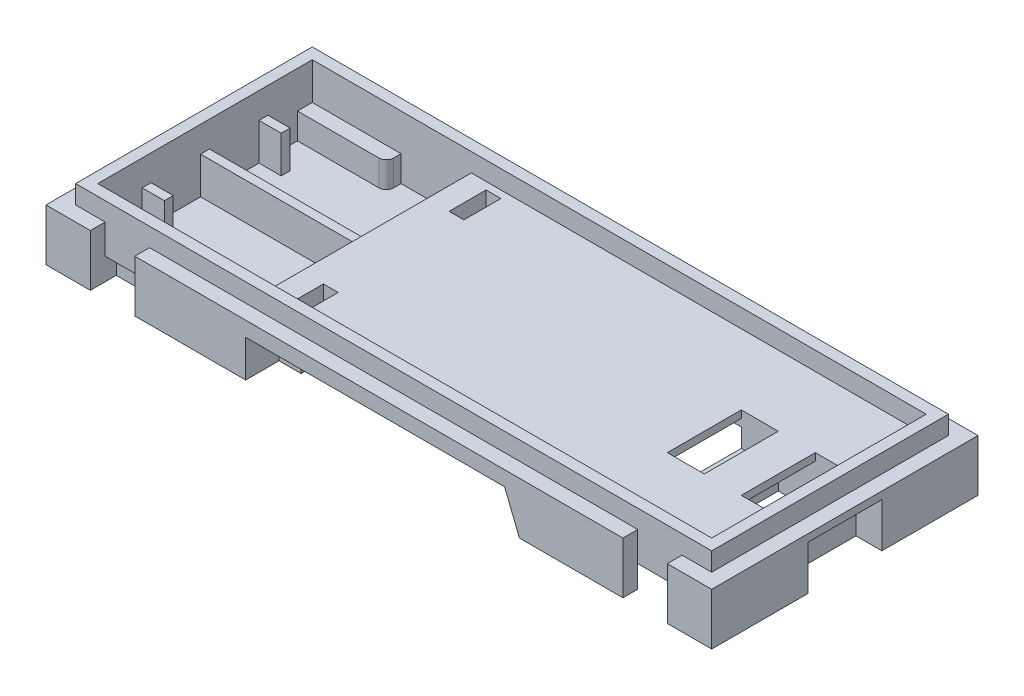
SolidWorks part; units mm, degrees
ref_plane "Спереди" through (0, 0, 0) normal (0, 0, 1) x (1, 0, 0)
ref_plane "Сверху" through (0, 0, 0) normal (0, 1, 0) x (1, 0, 0)
ref_plane "Справа" through (0, 0, 0) normal (1, 0, 0) x (0, 0, -1)
sketch "Эскиз1" plane through (0, 0, 0) normal (0, 1, 0) x (1, 0, 0)
  line L1 (45, -18) -> (-45, -18)
  line L2 (45, -18) -> (45, 18)
  line L3 (45, 18) -> (-45, 18)
  line L4 (-45, -18) -> (-45, 18)
  line L5 (45, -18) -> (-45, 18) construction
  line L6 (45, 18) -> (-45, -18) construction
  point P0 (0, 0)
  dimension "D1" = 90
  dimension "D2" = 36
extrude "Бобышка-Вытянуть1" add sketch "Эскиз1" along normal blind 7
sketch "Эскиз2" plane through (0, 7, 0) normal (0, 1, 0) x (1, 0, 0)
  line L1 (43, -16) -> (-43, -16)
  line L2 (43, -16) -> (43, 16)
  line L3 (43, 16) -> (-43, 16)
  line L4 (-43, -16) -> (-43, 16)
  line L5 (43, -16) -> (-43, 16) construction
  line L6 (43, 16) -> (-43, -16) construction
  point P0 (0, 0)
  dimension "D1" = 2
  dimension "D2" = 2
extrude "Вытянуть-Тонкостенный1" add sketch "Эскиз2" along normal blind 2.5 thin thin type one direction reverse wall 1.5
sketch "Эскиз3" plane through (0, 0, 18) normal (0, 0, 1) x (1, 0, 0)
  line L0 (-45, 0) -> (-18, 0) construction
  line L1 (-45, 0) -> (45, 0) construction
  line L2 (-18, 0) -> (-18, 5)
  line L3 (-18, 5) -> (17, 5)
  line L4 (17, 5) -> (19, 0)
  line L5 (-18, 0) -> (19, 0)
  dimension "D1" = 27
  dimension "D2" = 35
  dimension "D3" = 37
  dimension "D4" = 5
extrude "Вырез-Вытянуть1" cut sketch "Эскиз3" against normal up to surface (36 mm away) up to face at (0, 3.5, -18)
sketch "Эскиз4" plane through (45, 0, 0) normal (1, 0, 0) x (0, 0, -1)
  line L0 (0, 0) -> (0, 2.5) construction
  line L1 (-5, 2.5) -> (5, 2.5)
  line L2 (-5, 6) -> (5, 6)
  line L3 (-5, 6) -> (-5, 0)
  line L4 (-5, 0) -> (5, 0)
  line L5 (5, 6) -> (5, 0)
  point P7 (0, 0)
  line M2 (-18, 0) -> (18, 0)
  dimension "D1" = 2.5
  dimension "D2" = 6
  dimension "D3" = 10
  dimension "D4" = 2.5
extrude "Вырез-Вытянуть2" cut sketch "Эскиз4" against normal blind 3.5 contours L0 L1 L3 M2 | L0 L4 L5 L1 | L5 L2 L3 L1 region at (45, 1.25, 2.5) region at (45, 1.25, -2.5) region at (45, 4.25, 0)
extrude "Вырез-Вытянуть3" cut sketch "Эскиз4<3>" against normal blind 52 contours L5 L2 L3 L1 region at (45, 4.25, 0)
sketch "Эскиз4<3>" plane through (45, 0, 0) normal (1, 0, 0) x (0, 0, -1) same geometry as "Эскиз4"
sketch "Эскиз5" plane through (0, 0, 0) normal (0, -1, 0) x (1, 0, 0)
  line L0 (0, 0) -> (45, 0) construction
  line L1 (45, 5) -> (45, -5) construction
  line L2 (45, -7) -> (45, 7)
  line L3 (43, -16) -> (13, -16)
  line L4 (43, -16) -> (43, 16)
  line L5 (43, 16) -> (13, 16)
  line L6 (13, -16) -> (13, 16)
  line L7 (43, -16) -> (13, 16) construction
  line L8 (43, 16) -> (13, -16) construction
  line L9 (45, 18) -> (45, 5) construction
  line L10 (45, 7) -> (26, 7)
  line L11 (26, 7) -> (26, -7)
  line L12 (26, -7) -> (45, -7)
  line L13 (26, 0) -> (31, 0) construction
  line L14 (36, -5) -> (31, -5)
  line L15 (36, -5) -> (36, 5)
  line L16 (36, 5) -> (31, 5)
  line L17 (31, -5) -> (31, 5)
  line L18 (36, -5) -> (31, 5) construction
  line L19 (36, 5) -> (31, -5) construction
  point P5 (28, 0)
  point P10 (33.5, 0)
  point P16 (45, 0)
  line M10 (19, 18) -> (19, -18)
  dimension "D1" = 2
  dimension "D2" = 2
  dimension "D3" = 30
  dimension "D4" = 14
  dimension "D5" = 19
  dimension "D6" = 5
  dimension "D7" = 10
  dimension "D8" = 5
extrude "Вырез-Вытянуть4" cut sketch "Эскиз5" against normal up to surface (5 mm away) contours L12 L11 L10 L4 L5 L3 M10 | L6 L3 L5 M10 | L17 L14 L15 L16 region at (42.6, 0, -11.5) region at (16, 0, 0) region at (33.5, 0, 0) up to face at (2.25, 5, 0)
sketch "Эскиз6" plane through (0, 7, 0) normal (0, 1, 0) x (1, 0, 0)
  line L0 (-41.5, -14.5) -> (41.5, -14.5) construction
  line L1 (-41.5, 14.5) -> (-20, 14.5)
  line L2 (-41.5, 14.5) -> (-41.5, -14.5)
  line L3 (-41.5, -14.5) -> (-20, -14.5)
  line L4 (-20, 14.5) -> (-20, -14.5)
  dimension "D1" = 21.5
extrude "Вырез-Вытянуть5" cut sketch "Эскиз6" against normal blind 6
sketch "Эскиз7" plane through (0, 5, 0) normal (0, -1, 0) x (1, 0, 0)
  line L0 (43, 16) -> (17, 16) construction
  line L1 (24, 16) -> (20.5, 16)
  line L2 (24, 16) -> (24, 12)
  line L3 (24, 12) -> (20.5, 12)
  line L4 (20.5, 16) -> (20.5, 12)
  line L5 (43, 16) -> (19, 16) construction
  line L6 (45, 0) -> (0, 0) construction
  line L7 (45, 5) -> (45, -5) construction
  line L8 (24, -16) -> (20.5, -16)
  line L9 (24, -16) -> (24, -12)
  line L10 (24, -12) -> (20.5, -12)
  line L11 (20.5, -16) -> (20.5, -12)
  arc A0 (20.5, 14) -> (24, 14) centre (22.25, 13.7656) ccw
  arc A1 (20.5, -14) -> (24, -14) centre (22.25, -13.7656) cw
  line M7 (17, -16) -> (43, -16)
  line M17 (43, 16) -> (17, 16)
  dimension "D1" = 19
  dimension "D2" = 3.5
  dimension "D3" = 4
extrude "Бобышка-Вытянуть2" add sketch "Эскиз7" along normal blind 3 contours A0 L2 L4 M17 | A1 L11 L9 M7 region at (22.25, 5, 14.1643) region at (22.25, 5, -14.1643)
sketch "Эскиз8" plane through (-18, 0, 0) normal (1, 0, 0) x (0, 0, -1)
  line L0 (18, 0) -> (-18, 0) construction
  line L1 (-13.5, 0) -> (-8.5, 0)
  line L2 (-13.5, 0) -> (-13.5, 5)
  line L3 (-13.5, 5) -> (-8.5, 5)
  line L4 (-8.5, 0) -> (-8.5, 5)
  line L5 (18, 5) -> (-18, 5) construction
  line L6 (0, 0) -> (0, 5) construction
  line L7 (8.5, 0) -> (8.5, 5)
  line L8 (13.5, 0) -> (8.5, 0)
  line L9 (13.5, 5) -> (8.5, 5)
  line L10 (13.5, 0) -> (13.5, 5)
  dimension "D1" = 4.5
  dimension "D2" = 5
extrude "Бобышка-Вытянуть3" add sketch "Эскиз8" along normal blind 3
sketch "Эскиз9" plane through (0, 0, -13.5) normal (0, 0, -1) x (-1, 0, 0)
  line L0 (15, 5) -> (15, 2.2)
  line L1 (15, 0) -> (15, 5) construction
  line L2 (15, 2.2) -> (17, 3)
  line L3 (17, 3) -> (17, 5)
  line L4 (18, 5) -> (-17, 5) construction
  line L5 (17, 5) -> (15, 5)
  line L6 (15, 0) -> (18, 0) construction
  dimension "D1" = 2.2
  dimension "D2" = 3
  dimension "D3" = 1
extrude "Вырез-Вытянуть6" cut sketch "Эскиз9" against normal up to surface (27 mm away) up to face at (-16.5, 2.5, 13.5)
sketch "Эскиз10" plane through (-1.3103, -3.2759, 0) normal (0.3714, 0.9285, 0) x (0.9285, -0.3714, 0)
  line L0 (-14.7442, -10) -> (-14.7442, -12)
  line L1 (-14.7442, -13.5) -> (-14.7442, -8.5) construction
  line L2 (-14.7442, -12) -> (-16.8983, -12)
  line L3 (-16.8983, -13.5) -> (-16.8983, -8.5) construction
  line L4 (-14.7442, -10) -> (-16.8983, -10)
  line L5 (-16.8983, -10) -> (-16.8983, -12)
  point P5 (-14.7442, -11)
  point P10 (-14.7442, -11)
  dimension "D1" = 2
extrude "Бобышка-Вытянуть4" add sketch "Эскиз10" along direction (0, -1, 0) on the side of the normal blind 0.5
mirror "Зеркальное отражение1" about plane through (0, 0, 0) normal (0, 0, 1) of "Бобышка-Вытянуть4"
sketch "Эскиз12" plane through (0, 0, 0) normal (0, -1, 0) x (-1, 0, 0)
  line L0 (15, -8.5) -> (18, -8.5) construction
  line L1 (15, -13.5) -> (17, -13.5)
  line L2 (15, -13.5) -> (15, -8.5)
  line L3 (15, -8.5) -> (17, -8.5)
  line L4 (17, -13.5) -> (17, -8.5)
  dimension "D1" = 1
extrude "Вырез-Вытянуть10" cut sketch "Эскиз12" against normal up to surface (7 mm away) from surface up to face at (10.75, 7, 0) starting at face at (10.375, 5, 0)
mirror "Зеркальное отражение2" about plane through (0, 0, 0) normal (0, 0, 1) of "Вырез-Вытянуть10"
sketch "Эскиз13" plane through (0, 0, 0) normal (0, -1, 0) x (1, 0, 0)
  line L1 (31, -5) -> (26, -5)
  line L2 (31, -5) -> (31, 5)
  line L3 (31, 5) -> (26, 5)
  line L4 (26, -5) -> (26, 5)
  line L5 (36, -5) -> (41.5, -5)
  line L6 (36, -5) -> (36, 5)
  line L7 (36, 5) -> (41.5, 5)
  line L8 (41.5, -5) -> (41.5, 5)
extrude "Вырез-Вытянуть11" cut sketch "Эскиз13" against normal up to surface (7 mm away) from surface up to face at (-16, 7, -11) starting at face at (19, 6, 0)
sketch "Эскиз14" plane through (0, 7, 0) normal (0, 1, 0) x (1, 0, 0)
  line L0 (43, 16) -> (-43, 16) construction
  line L1 (-39, 16) -> (-33, 16)
  line L2 (-39, 16) -> (-39, 18)
  line L3 (-39, 18) -> (-33, 18)
  line L4 (-33, 16) -> (-33, 18)
  line L5 (45, 18) -> (-45, 18) construction
  line L6 (0, 0) -> (-45, 0) construction
  line L7 (39, 16) -> (33, 16)
  line L8 (39, 16) -> (39, 18)
  line L9 (39, 18) -> (33, 18)
  line L10 (33, 16) -> (33, 18)
  line L11 (-45, 18) -> (-45, -18) construction
  line L12 (33, -16) -> (33, -18)
  line L13 (39, -18) -> (33, -18)
  line L14 (39, -16) -> (39, -18)
  line L15 (39, -16) -> (33, -16)
  line L16 (-33, -16) -> (-33, -18)
  line L17 (-39, -18) -> (-33, -18)
  line L18 (-39, -16) -> (-39, -18)
  line L19 (-39, -16) -> (-33, -16)
  dimension "D1" = 6
  dimension "D2" = 6
  dimension "D3" = 6
  dimension "D4" = 6
extrude "Вырез-Вытянуть12" cut sketch "Эскиз14" against normal up to surface (7 mm away) up to face at (-21.5, 0, 0)
sketch "Эскиз16" plane through (0, 5, 0) normal (0, -1, 0) x (1, 0, 0)
  line L0 (43, 16) -> (39, 16) construction
  line L1 (33, 16) -> (39, 16) construction
  line L2 (36, 16) -> (36, 7) construction
  line L3 (43, 7) -> (26, 7) construction
  line L4 (31, 14) -> (41, 14)
  line L5 (31, 14) -> (31, 16)
  line L6 (31, 16) -> (41, 16)
  line L7 (41, 14) -> (41, 16)
  line L8 (31, 14) -> (41, 16) construction
  line L9 (31, 16) -> (41, 14) construction
  line L10 (0, 0) -> (45, 0) construction
  line L11 (45, 5) -> (45, -5) construction
  line L12 (41, -14) -> (41, -16)
  line L13 (31, -16) -> (41, -16)
  line L14 (31, -14) -> (31, -16)
  line L15 (31, -14) -> (41, -14)
  point P6 (36, 15)
  dimension "D1" = 10
  dimension "D2" = 2
extrude "Бобышка-Вытянуть5" add sketch "Эскиз16" along normal blind 2
sketch "Эскиз17" plane through (0, 1, 0) normal (0, 1, 0) x (1, 0, 0)
  line L0 (0, 0) -> (-43, 0) construction
  line L1 (-41.5, 14.5) -> (-29.5, 14.5)
  line L2 (-41.5, 14.5) -> (-41.5, 12.5)
  line L3 (-41.5, 12.5) -> (-29.5, 12.5)
  line L4 (-29.5, 14.5) -> (-29.5, 12.5)
  line L5 (-43, 16) -> (-43, -16) construction
  line L6 (-29.5, -14.5) -> (-29.5, -12.5)
  line L7 (-41.5, -14.5) -> (-41.5, -12.5)
  line L8 (-41.5, -14.5) -> (-29.5, -14.5)
  line L9 (-41.5, -12.5) -> (-29.5, -12.5)
  dimension "D1" = 2
  dimension "D2" = 12
extrude "Бобышка-Вытянуть6" add sketch "Эскиз17" along normal blind 3.5
sketch "Эскиз15" plane through (0, 0, 0) normal (0, -1, 0) x (-1, 0, 0)
  line L0 (0, 0) -> (45, 0) construction
  line L1 (39, -16) -> (33, -16)
  line L2 (39, -16) -> (39, -14.5)
  line L3 (39, -14.5) -> (33, -14.5)
  line L4 (33, -16) -> (33, -14.5)
  line L5 (45, 18) -> (45, -18) construction
  line L6 (33, 16) -> (33, 14.5)
  line L7 (39, 14.5) -> (33, 14.5)
  line L8 (39, 16) -> (39, 14.5)
  line L9 (39, 16) -> (33, 16)
  dimension "D1" = 1.5
extrude "Вырез-Вытянуть13" cut sketch "Эскиз15" against normal blind 3
sketch "Эскиз19" plane through (0, 1, 0) normal (0, 1, 0) x (1, 0, 0)
  line L0 (-20, 0) -> (-41.5, 0)
  line L1 (-20, -14.5) -> (-20, 14.5) construction
  line L2 (-41.5, 14.5) -> (-41.5, -14.5) construction
  line L3 (-41.5, 12.5) -> (-41.5, -12.5) construction
  line L4 (-20, 0.6) -> (-41.5, 0.6)
  line L5 (-20, 0.6) -> (-20, -0.6)
  line L6 (-20, -0.6) -> (-41.5, -0.6)
  line L7 (-41.5, 0.6) -> (-41.5, -0.6)
  line L8 (-20, 0.6) -> (-41.5, -0.6) construction
  line L9 (-20, -0.6) -> (-41.5, 0.6) construction
  line L10 (-41.5, 8.5) -> (-41.5, 7.3)
  line L11 (-41.5, -8.5) -> (-38.5, -8.5)
  line L12 (-41.5, -8.5) -> (-41.5, -7.3)
  line L13 (-41.5, -7.3) -> (-38.5, -7.3)
  line L14 (-38.5, -8.5) -> (-38.5, -7.3)
  line L15 (-38.5, 8.5) -> (-38.5, 7.3)
  line L16 (-41.5, 7.3) -> (-38.5, 7.3)
  line L17 (-41.5, 8.5) -> (-38.5, 8.5)
  point P6 (-30.75, 0)
  line M5 (-20, -14.5) -> (-20, 14.5)
  line M9 (-41.5, 12.5) -> (-41.5, -12.5)
  dimension "D1" = 1.2
  dimension "D2" = 4
  dimension "D3" = 1.2
  dimension "D4" = 3
extrude "Бобышка-Вытянуть7" add sketch "Эскиз19" along normal blind 5 contours L6 L0 M5 M9 | L4 L0 M5 M9 | L11 L14 L13 M9 | L17 L16 L15 M9 region at (-30.75, 1, 0.3) region at (-30.75, 1, -0.3) region at (-40, 1, 7.9) region at (-40, 1, -7.9)
fillet "Скругление1" radius 1 1 edges at (31, 4, -14) type face fillet first side face at (36, 4, -14) second side face at (31, 4, -15)
fillet "Скругление2" radius 1 1 edges at (41, 4, -14) type face fillet first side face at (36.5, 4, -14) second side face at (41, 4, -15)
fillet "Скругление3" radius 1 1 edges at (31, 4, 14) type face fillet first side face at (31, 4, 15) second side face at (36, 4, 14)
fillet "Скругление4" radius 1 1 edges at (41, 4, 14) type face fillet first side face at (36.5, 4, 14) second side face at (41, 4, 15)
fillet "Скругление5" radius 1 1 edges at (-29.5, 2.75, -12.5) type face fillet first side face at (-35.5, 2.75, -12.5) second side face at (-29.5, 2.75, -13.5)
fillet "Скругление6" radius 1 1 edges at (-29.5, 2.75, 12.5) type face fillet first side face at (-29.5, 2.75, 13.5) second side face at (-35.5, 2.75, 12.5)
equation "\"width\"=36"
equation "\"D2@Эскиз1\"=\"width\""
